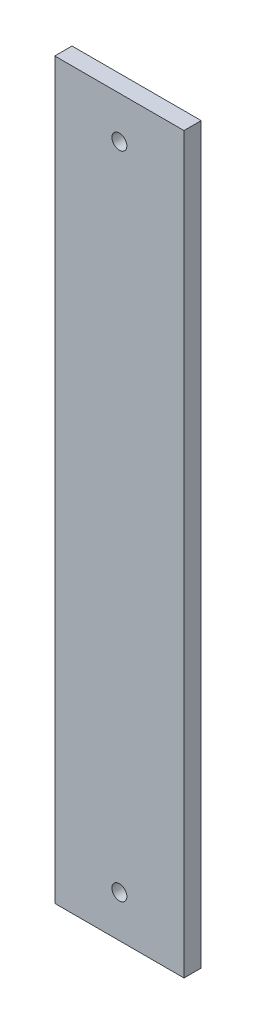
SolidWorks part; units mm, degrees
material "MDF"
ref_plane "Plano frontal" through (0, 0, 0) normal (0, 0, 1) x (1, 0, 0)
ref_plane "Plano superior" through (0, 0, 0) normal (0, 1, 0) x (1, 0, 0)
ref_plane "Plano direito" through (0, 0, 0) normal (1, 0, 0) x (0, 0, -1)
sketch "Esboço1" plane through (0, 0, 0) normal (0, 0, 1) x (1, 0, 0)
  line L1 (-22.5, -127.8) -> (22.5, -127.8)
  line L2 (-22.5, -127.8) -> (-22.5, 127.8)
  line L3 (-22.5, 127.8) -> (22.5, 127.8)
  line L4 (22.5, -127.8) -> (22.5, 127.8)
  line L5 (-22.5, -127.8) -> (22.5, 127.8) construction
  line L6 (-22.5, 127.8) -> (22.5, -127.8) construction
  line L7 (0, 0) -> (22.5, 0) construction
  circle A1 centre (0, 113.2) radius 2.6
  circle A2 centre (0, -113.2) radius 2.6
  point P0 (0, 0)
  point P11 (0, 127.8)
  dimension "D2" = 14.6
  dimension "D3" = 5.2
  dimension "D1" = 255.6
  dimension "D4" = 45
extrude "Ressalto-extrusão1" add sketch "Esboço1" along normal blind 6
